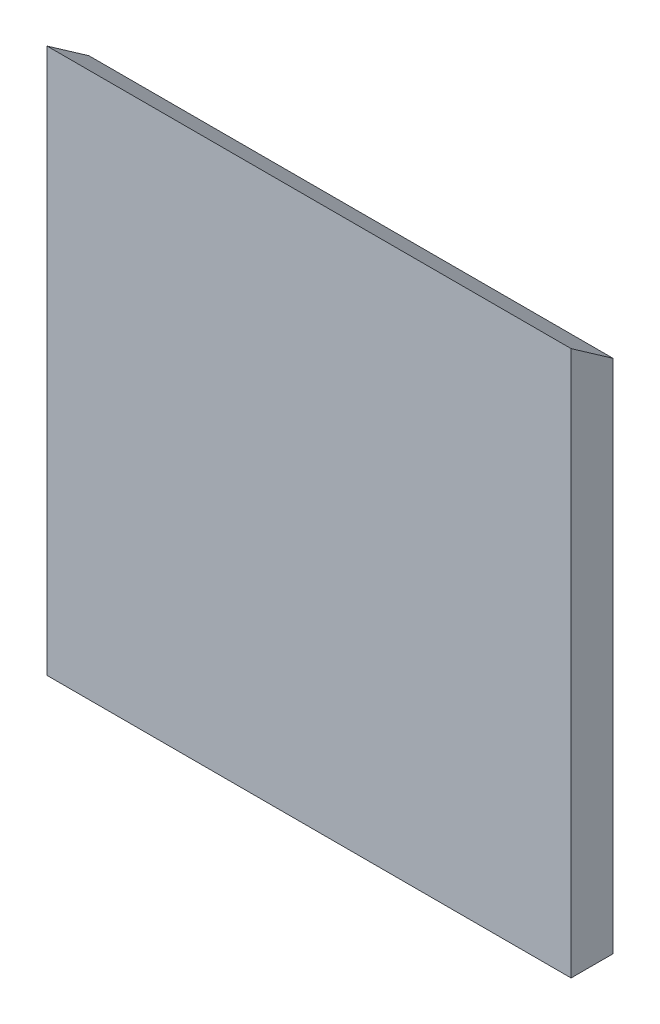
SolidWorks part; units mm, degrees
ref_plane "Plan de face" through (0, 0, 0) normal (0, 0, 1) x (1, 0, 0)
ref_plane "Plan de dessus" through (0, 0, 0) normal (0, 1, 0) x (1, 0, 0)
ref_plane "Plan de droite" through (0, 0, 0) normal (1, 0, 0) x (0, 0, -1)
sketch "Esquisse1" plane through (0, 0, 0) normal (0, 0, 1) x (1, 0, 0)
  line L1 (0, 0) -> (125, 0)
  line L2 (0, 0) -> (0, 130)
  line L3 (0, 130) -> (125, 130)
  line L4 (125, 0) -> (125, 130)
  dimension "D1" = 125
  dimension "D2" = 130
extrude "Boss.-Extru.1" add sketch "Esquisse1" along normal blind 10
chamfer "Chanfrein1" distance 10 angle 35 1 edges at (62.5, 130, 0) first distance on face at (62.5, 130, 5)
fillet "Congé1" [suppressed] radius 5
fillet "Congé2" [suppressed] radius 5
